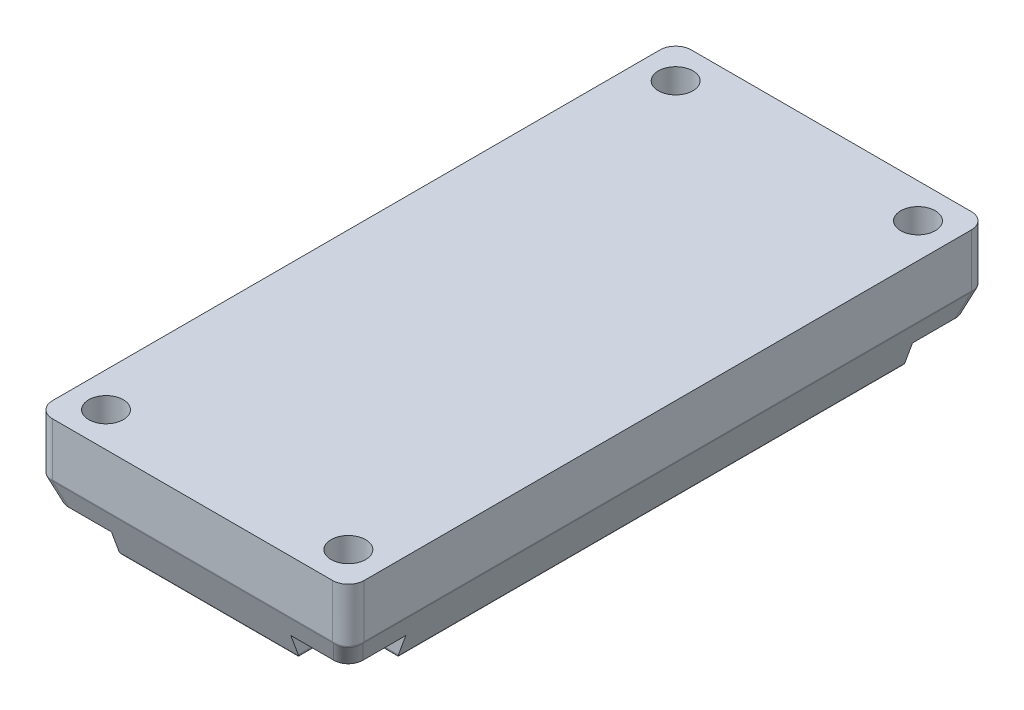
SolidWorks part; units mm, degrees
material "Polyethylene Cross-Linked"
ref_plane "Front Plane" through (0, 0, 0) normal (0, 0, 1) x (1, 0, 0)
ref_plane "Top Plane" through (0, 0, 0) normal (0, 1, 0) x (1, 0, 0)
ref_plane "Right Plane" through (0, 0, 0) normal (1, 0, 0) x (0, 0, -1)
sketch "Sketch1" plane through (0, 0, 0) normal (0, 1, 0) x (1, 0, 0)
  line L1 (-9.9, 20.3) -> (9.9, 20.3)
  line L2 (-9.9, 20.3) -> (-9.9, -20.3)
  line L3 (-9.9, -20.3) -> (9.9, -20.3)
  line L4 (9.9, 20.3) -> (9.9, -20.3)
  line L5 (-9.9, 20.3) -> (9.9, -20.3) construction
  line L6 (-9.9, -20.3) -> (9.9, 20.3) construction
  point P0 (0, 0)
  dimension "D1" = 19.8
  dimension "D2" = 40.6
extrude "Boss-Extrude1" add sketch "Sketch1" against normal blind 6.4
sketch "Sketch2" plane through (0, -6.4, 0) normal (0, -1, 0) x (-1, 0, 0)
  line L0 (5.7, -17.9) -> (5.7, -20.3)
  line L1 (9.9, -20.3) -> (-9.9, -20.3) construction
  line L2 (7.5, -16.1) -> (9.9, -16.1)
  line L3 (9.9, 20.3) -> (9.9, -20.3) construction
  line L4 (5.7, -20.3) -> (9.9, -20.3)
  line L5 (9.9, -20.3) -> (9.9, -16.1)
  arc A0 (7.5, -16.1) -> (5.7, -17.9) centre (7.5, -17.9) ccw
  dimension "D3" = 3.6
  dimension "D1" = 4.2
  dimension "D2" = 4.2
extrude "Cut-Extrude1" cut sketch "Sketch2" against normal blind 1.5
hole_wizard "M2 Clearance Hole1" positions "Sketch8" profile "Sketch7" hole size "M2" standard "ANSI Metric" end condition through all
sketch "Sketch8" plane through (0, -4.9, 0) normal (0, -1, 0) x (-1, 0, 0)
  line L0 (9.9, -20.3) -> (9.9, -16.1) construction
  line L1 (5.7, -20.3) -> (9.9, -20.3) construction
  point P0 (7.7, -18.1)
  dimension "D1" = 2.2
  dimension "D2" = 2.2
sketch "Sketch7" plane through (-7.7, -4.9, 18.1) normal (1, 0, 0) x (0, 0, -1)
  line L0 (0, 0) -> (0, 4.9)
  line L1 (0, 4.9) -> (1.1, 4.9)
  line L2 (1.1, 4.9) -> (1.1, 0)
  line L5 (1.1, 0) -> (0, 0)
  line L11 (0, -6.35) -> (0, 107.95) construction
  dimension "Thru Hole Dia." = 2.2
  dimension "Thru Hole Depth" = 4.9
mirror "Mirror1" about plane through (0, 0, 0) normal (1, 0, 0) of "M2 Clearance Hole1", "Cut-Extrude1"
mirror "Mirror2" about plane through (0, 0, 0) normal (0, 0, 1) of "Mirror1", "Cut-Extrude1"
sketch "Sketch3" plane through (0, 0, 0) normal (0, 0, 1) x (1, 0, 0)
  line L0 (9.9, -3.4) -> (9.9, -6.4)
  line L1 (9.9, -4.9) -> (9.9, 0) construction
  line L2 (9.9, -6.4) -> (8.8081, -6.4)
  line L3 (9.9, -6.4) -> (7.5, -6.4) construction
  line L4 (8.8081, -6.4) -> (9.9, -3.4)
  dimension "D1" = 3
  dimension "D2" = 20
extrude "Cut-Extrude2" cut sketch "Sketch3" against normal through all both and the other way through all
mirror "Mirror3" about plane through (0, 0, 0) normal (1, 0, 0) of "Cut-Extrude2"
sketch "Sketch4" plane through (0, 0, 0) normal (1, 0, 0) x (0, 0, -1)
  line L0 (20.3, -3.4) -> (19.2081, -6.4)
  line L1 (20.3, -3.4) -> (20.3, 0) construction
  line L2 (17.9, -6.4) -> (20.3, -6.4) construction
  line L3 (19.2081, -6.4) -> (20.3, -6.4)
  line L4 (20.3, -6.4) -> (20.3, -3.4)
  dimension "D1" = 3
  dimension "D2" = 20
extrude "Cut-Extrude3" cut sketch "Sketch4" against normal through all both and the other way through all
mirror "Mirror4" about plane through (0, 0, 0) normal (0, 0, 1) of "Cut-Extrude3"
fillet "Fillet1" radius 1 8 edges at (-9.627, -4.15, -20.027) (-9.9, -1.7, -20.3) (9.9, -1.7, -20.3) (9.627, -4.15, -20.027) (9.627, -4.15, 20.027) (9.9, -1.7, 20.3) (-9.9, -1.7, 20.3) (-9.627, -4.15, 20.027)
fillet "Fillet2" radius 0.2 32 edges at (-8.9293, -3.4012, 20.2996) (-9.6071, -3.4659, 20.0071) (-9.8996, -3.4012, 19.3293) (-9.9, -3.4, 0) (-9.8996, -3.4012, -19.3293) (-9.6071, -3.4659, -20.0071) (-8.9293, -3.4012, -20.2996) (0, -3.4, -20.3) (8.9293, -3.4012, -20.2996) (9.6071, -3.4659, -20.0071) (9.8996, -3.4012, -19.3293) (9.9, -3.4, 0) (9.8996, -3.4012, 19.3293) (9.6071, -3.4659, 20.0071) (8.9293, -3.4012, 20.2996) (5.7, -6.4, 18.554) (6.2272, -6.4, 16.6272) (8.154, -6.4, 16.1) (8.8081, -6.4, 0) (8.154, -6.4, -16.1) (6.2272, -6.4, -16.6272) (5.7, -6.4, -18.554) (0, -6.4, -19.2081) (-5.7, -6.4, -18.554) (-6.2272, -6.4, -16.6272) (-8.154, -6.4, -16.1) (-8.8081, -6.4, 0) (-8.154, -6.4, 16.1) (-6.2272, -6.4, 16.6272) (-5.7, -6.4, 18.554) (0, -6.4, 19.2081) (0, -3.4, 20.3)
